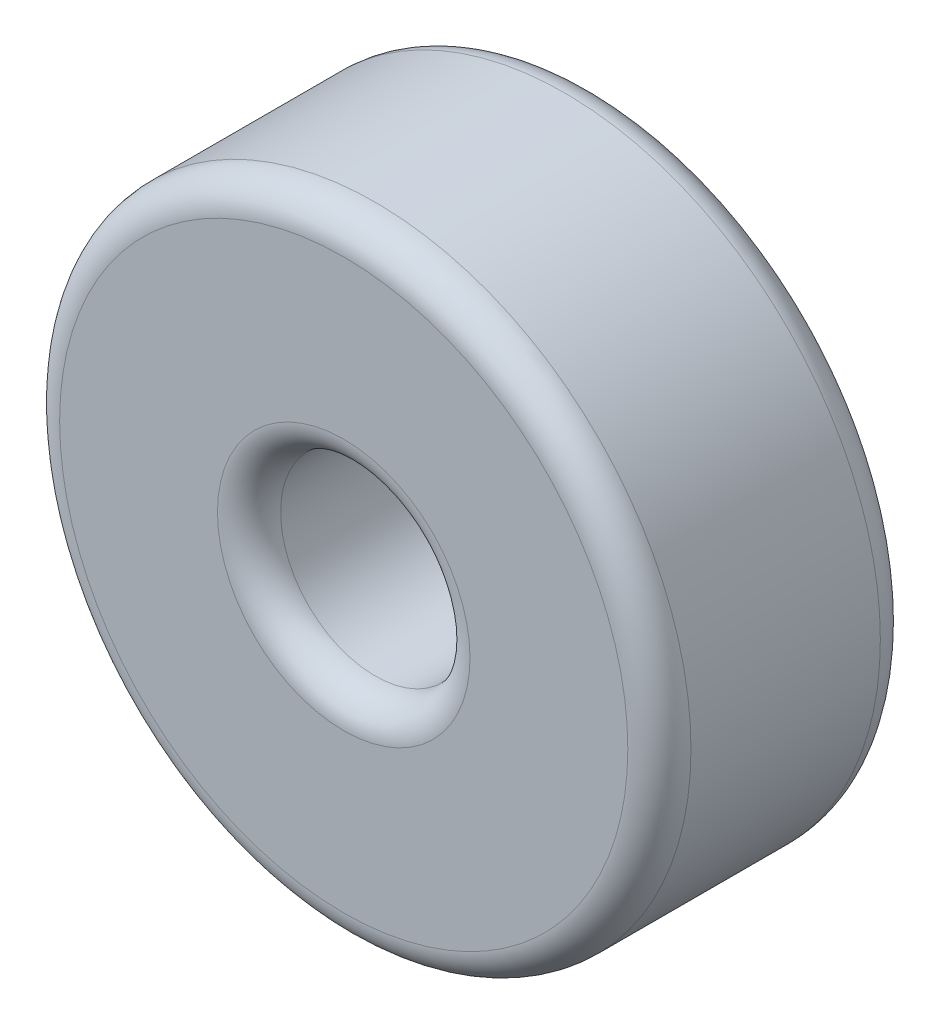
SolidWorks part; units mm, degrees
ref_plane "Спереди" through (0, 0, 0) normal (0, 0, 1) x (1, 0, 0)
ref_plane "Сверху" through (0, 0, 0) normal (0, 1, 0) x (1, 0, 0)
ref_plane "Справа" through (0, 0, 0) normal (1, 0, 0) x (0, 0, -1)
sketch "Эскиз1" plane through (0, 0, 0) normal (0, 0, 1) x (1, 0, 0)
  circle A0 centre (0, 0) radius 1.5
  circle A1 centre (0, 0) radius 5
  dimension "D1" = 3
  dimension "D2" = 10
extrude "Бобышка-Вытянуть1" add sketch "Эскиз1" along normal blind 4
fillet "Скругление1" radius 0.5 4 edges at (1.5, 0, 0) (5, 0, 0) (1.5, 0, 4) (5, 0, 4)
